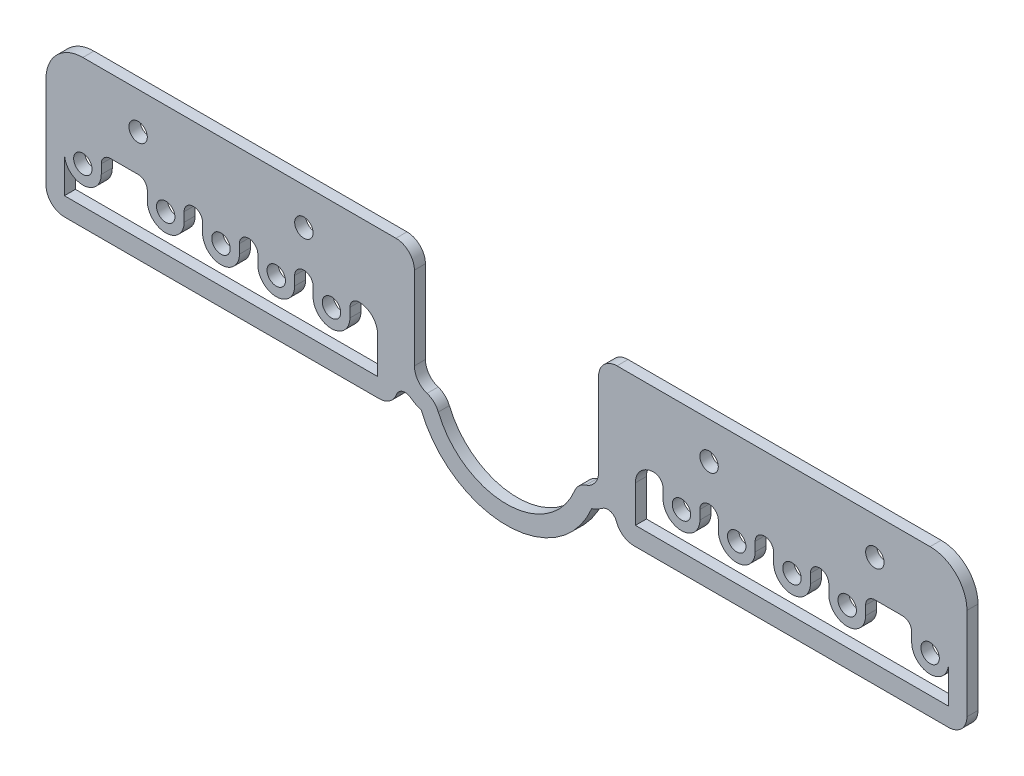
SolidWorks part; units mm, degrees
ref_plane "Front Plane" through (0, 0, 0) normal (0, 0, 1) x (1, 0, 0)
ref_plane "Top Plane" through (0, 0, 0) normal (0, 1, 0) x (1, 0, 0)
ref_plane "Right Plane" through (0, 0, 0) normal (1, 0, 0) x (0, 0, -1)
sketch "Sketch1" plane through (0, 0, 0) normal (0, 0, 1) x (1, 0, 0)
  line L0 (-40, 20) -> (-40, 55) construction
  line L4 (-250, -55) -> (-250, 3.1783)
  line L8 (-50, 75) -> (-230, 75) construction
  line L17 (0, -20) -> (0, -40)
  line L25 (0, -65) -> (0, -75)
  line L26 (0, 75) -> (0, -75) construction
  line L27 (-50, 95) -> (50, 95) construction
  line L34 (0, -75) -> (-230, -75)
  line L156 (-50, 75) -> (-230, 75) construction
  line L161 (0, -40) -> (0, -65)
  line L165 (-164.3309, 75) -> (-60, 75)
  line L167 (-230, 75) -> (-220, 75)
  line L171 (-250, 3.1783) -> (-250, 55)
  line L172 (-220, 75) -> (-164.3309, 75)
  line L173 (-50, 65) -> (-50, 20)
  arc A0 (-40, 20) -> (0, -20) centre (0, 20) ccw construction
  circle A1 centre (0, 20) radius 30 construction
  arc A4 (-230, -75) -> (-250, -55) centre (-230, -55) cw
  arc A5 (-250, 55) -> (-230, 75) centre (-230, 55) cw
  arc A124 (0, -20) -> (-37, 4.8013) centre (0, 20) cw
  arc A125 (-60, 75) -> (-50, 65) centre (-60, 65) cw
  arc A126 (-43.125, 10.5008) -> (-50, 20) centre (-40, 20) cw
  arc A127 (-37, 4.8013) -> (-43.125, 10.5008) centre (-46.25, 1.0016) ccw
  point P0 (0, 0)
  point P10 (-50, 10)
  point P11 (0, 50)
  point P30 (-40, 75)
  point P45 (0, -30)
  point P74 (0, 95)
  dimension "D3" = 80
  dimension "D4" = 60
  dimension "D6" = 55
  dimension "D7" = 75
  dimension "D10" = 10
  dimension "D11" = 20
  dimension "D8" = 10
  dimension "D5" = 10
  dimension "D9" = 20
  dimension "D13" = 210
  dimension "D16" = 100
  dimension "D17" = 20
  dimension "D26" = 250
extrude "Boss-Extrude1" add sketch "Sketch1" along normal blind 6
mirror "Mirror1" about plane through (0, -20, 6) normal (-1, 0, 0) of "Boss-Extrude1"
sketch "Sketch3" plane through (0, 0, 6) normal (0, 0, 1) x (1, 0, 0)
  line L3 (50, 20) -> (50, 65) construction
  line L4 (50, 20) -> (50, 65) construction
  line L7 (-60, 75) -> (-230, 75) construction
  line L8 (-250, 55) -> (-250, -55) construction
  line L9 (250, 55) -> (250, -55) construction
  circle A2 centre (110, 55) radius 5
  circle A3 centre (200, 55) radius 5
  circle A4 centre (-200, 55) radius 5
  circle A5 centre (-110, 55) radius 5
  dimension "D3" = 10
  dimension "D4" = 10
  dimension "D5" = 10
  dimension "D6" = 10
  dimension "D8" = 20
  dimension "D12" = 50
  dimension "D2" = 140
  dimension "D7" = 20
  dimension "D9" = 50
  dimension "D10" = 140
extrude "Cut-Extrude1" cut sketch "Sketch3" against normal through all contours A2 | A3 | A5 | A4 region at (110, 55, 6) region at (200, 55, 6) region at (-110, 55, 6)
sketch "Sketch4" plane through (0, 0, 6) normal (0, 0, 1) x (1, 0, 0)
  line L0 (-230, -75) -> (230, -75) construction
  line L1 (-70, 25) -> (-70, -55)
  line L2 (-50, 20) -> (-50, 65) construction
  line L3 (-60, 75) -> (-230, 75) construction
  line L7 (-240, -55) -> (-240, 25)
  line L8 (-250, 55) -> (-250, -55) construction
  line L9 (-210, -65) -> (-190, -65)
  line L10 (-115, 25) -> (-115, 30)
  line L11 (-110, 35) -> (-80, 35)
  line L12 (-220, 25) -> (-220, 30)
  line L13 (-215, 35) -> (-140, 35)
  line L14 (-135, 30) -> (-135, 25)
  line L15 (-230, -65) -> (-210, -65)
  line L16 (-110, -65) -> (-90, -65)
  line L17 (0, 0) -> (0, -75) construction
  line L18 (-190, -65) -> (-110, -65)
  line L19 (90, -65) -> (80, -65)
  line L20 (190, -65) -> (110, -65)
  line L21 (-90, -65) -> (-80, -65)
  line L22 (110, -65) -> (90, -65)
  line L23 (230, -65) -> (210, -65)
  line L24 (230, 25) -> (125, 25) construction
  line L30 (221.3397, 20) -> (133.6603, 20)
  line L32 (110, 35) -> (80, 35)
  line L33 (115, 25) -> (115, 30)
  line L35 (210, -65) -> (190, -65)
  line L36 (240, -55) -> (240, 25)
  line L37 (70, 25) -> (70, -55)
  line L38 (125, 35) -> (230, 35)
  line L39 (230, 20) -> (125, 20) construction
  circle A0 centre (-230, 25) radius 5
  circle A3 centre (-125, 25) radius 5
  arc A6 (-230, -65) -> (-240, -55) centre (-230, -55) cw
  arc A8 (-222.2775, 18.6468) -> (-231.6408, 15.1355) centre (-230, 25) ccw
  arc A9 (-127.2754, 15.2623) -> (-127.1893, 15.2426) centre (-125, 25) ccw
  arc A12 (-110, 35) -> (-115, 30) centre (-110, 30) ccw
  arc A13 (-140, 35) -> (-135, 30) centre (-140, 30) cw
  arc A14 (-215, 35) -> (-220, 30) centre (-215, 30) ccw
  arc A15 (-70, -55) -> (-80, -65) centre (-80, -55) cw
  arc A16 (-70, 25) -> (-80, 35) centre (-80, 25) ccw
  arc A17 (-117.6445, 18.2253) -> (-134.5708, 22.1017) centre (-125, 25) ccw
  arc A19 (-231.6408, 15.1355) -> (-222.2775, 18.6468) centre (-230, 25) ccw
  arc A20 (-134.5708, 22.1017) -> (-117.3815, 18.5225) centre (-125, 25) ccw
  arc A21 (133.6603, 20) -> (117.3815, 18.5225) centre (125, 25) cw
  arc A22 (231.6408, 15.1355) -> (222.2775, 18.6468) centre (230, 25) cw
  arc A23 (117.6445, 18.2253) -> (125, 35) centre (125, 25) cw
  arc A24 (70, 25) -> (80, 35) centre (80, 25) cw
  arc A25 (70, -55) -> (80, -65) centre (80, -55) ccw
  arc A26 (230, 35) -> (231.6408, 15.1355) centre (230, 25) cw
  arc A28 (110, 35) -> (115, 30) centre (110, 30) cw
  arc A29 (127.2754, 15.2623) -> (127.1893, 15.2426) centre (125, 25) cw
  arc A30 (222.2775, 18.6468) -> (221.3397, 20) centre (230, 25) cw
  arc A31 (230, -65) -> (240, -55) centre (230, -55) ccw
  circle A32 centre (125, 25) radius 5
  circle A33 centre (230, 25) radius 5
  point P0 (0, -75)
  dimension "D1" = 10
  dimension "D13" = 10
  dimension "D14" = 20
  dimension "D10" = 5
  dimension "D15" = 5
  dimension "D17" = 10
  dimension "D2" = 230
  dimension "D4" = 5
  dimension "D5" = 125
  dimension "D8" = 50
  dimension "D9" = 10
  dimension "D11" = 20
  dimension "D12" = 80
  dimension "D16" = 80
extrude "Cut-Extrude2" cut sketch "Sketch4" against normal through all contours A20 A17 L14 A13 L13 A14 L12 A8 A19 L7 A6 L15 L9 L18 L16 L21 A15 L1 A16 L11 A12 L10 A9 | A0 | A3 region at (-154.1168, -16.7892, 6) region at (-230, 25, 6) region at (-125, 25, 6)
sketch "Sketch8" plane through (0, 0, 6) normal (0, 0, 1) x (1, 0, 0)
  line L0 (-60, 0) -> (-60, -65)
  line L2 (-60, -65) -> (60, -65)
  line L3 (60, -65) -> (60, 0)
  line L4 (-230, -65) -> (-80, -65) construction
  arc A0 (43.125, 10.5008) -> (50, 20) centre (40, 20) ccw construction
  arc A1 (43.125, 10.5008) -> (37, 4.8013) centre (46.25, 1.0016) ccw construction
  arc A2 (-37, 4.8013) -> (-43.125, 10.5008) centre (-46.25, 1.0016) ccw construction
  arc A3 (-50, 20) -> (-43.125, 10.5008) centre (-40, 20) ccw construction
  arc A4 (-37, 4.8013) -> (37, 4.8013) centre (0, 20) ccw construction
  arc A5 (43.125, 10.5008) -> (50, 20) centre (40, 20) ccw construction
  arc A6 (43.125, 10.5008) -> (37, 4.8013) centre (46.25, 1.0016) ccw construction
  arc A7 (-37, 4.8013) -> (-43.125, 10.5008) centre (-46.25, 1.0016) ccw construction
  arc A8 (-50, 20) -> (-43.125, 10.5008) centre (-40, 20) ccw construction
  arc A9 (-37, 4.8013) -> (37, 4.8013) centre (0, 20) ccw construction
  arc A10 (-52, 4) -> (-46.25, 1.0016) centre (-40, 20) ccw
  arc A11 (-46.25, 1.0016) -> (-46.25, 1.0016) centre (-46.25, 1.0016) ccw
  arc A12 (-46.25, 1.0016) -> (46.25, 1.0016) centre (0, 20) ccw
  arc A13 (46.25, 1.0016) -> (46.25, 1.0016) centre (46.25, 1.0016) ccw
  arc A14 (46.25, 1.0016) -> (52, 4) centre (40, 20) ccw
  arc A15 (46.25, 1.0016) -> (60, 20) centre (40, 20) ccw construction
  arc A16 (60, 0) -> (52, 4) centre (55, 0) ccw
  arc A17 (-60, 20) -> (-46.25, 1.0016) centre (-40, 20) ccw construction
  arc A18 (-60, 0) -> (-52, 4) centre (-55, 0) cw
  dimension "D2" = 5
  dimension "D1" = 10
extrude "Cut-Extrude5" cut sketch "Sketch8" against normal through all
fillet "Fillet5" radius 5 1 edges at (-60, -65, 3)
fillet "Fillet6" radius 5 1 edges at (60, -65, 3)
mirror "Mirror2" about plane through (0, 0, 0) normal (1, 0, 0) of "Cut-Extrude2"
sketch "Sketch9" plane through (0, 0, 6) normal (0, 0, 1) x (1, 0, 0)
  line L0 (-250, 5) -> (-70, 5)
  line L1 (-250, 55) -> (-250, -55) construction
  line L2 (250, 55) -> (250, -55) construction
  line L3 (250, 5) -> (250, -5)
  line L4 (250, -5) -> (70, -5)
  line L5 (-250, -5) -> (-250, 5)
  line L6 (-215, 35) -> (-140, 35) construction
  line L7 (-70, 5) -> (-70, -5)
  line L8 (-70, 25) -> (-70, -55) construction
  line L9 (70, 5) -> (70, -5)
  line L10 (70, 25) -> (70, -55) construction
  line L11 (70, 5) -> (250, 5)
  line L12 (-70, -5) -> (-250, -5)
  dimension "D1" = 10
  dimension "D2" = 30
extrude "Boss-Extrude2" add sketch "Sketch9" against normal up to surface (6 mm away) up to face at (225, 25, 0)
sketch "Sketch10" plane through (0, 0, 6) normal (0, 0, 1) x (1, 0, 0)
  line L0 (-240, -5) -> (-250, -5)
  line L1 (-250, 55) -> (-250, -55) construction
  line L2 (-250, -5) -> (-250, -78.6459)
  line L3 (-250, -78.6459) -> (262.9132, -78.6459)
  line L4 (262.9132, -78.6459) -> (262.9132, -5)
  line L5 (262.9132, -5) -> (43.3013, -5)
  line L7 (-43.3013, -5) -> (-240, -5)
  arc A0 (-46.25, 1.0016) -> (46.25, 1.0016) centre (0, 20) ccw construction
  arc A1 (-43.3013, -5) -> (43.3013, -5) centre (0, 20) ccw
  point P14 (0, 0)
extrude "Cut-Extrude6" cut sketch "Sketch10" against normal through all
fillet "Fillet7" radius 10 4 edges at (60, -5, 3) (250, -5, 3) (-60, -5, 3) (-250, -5, 3)
sketch "Sketch11" plane through (0, 0, 6) normal (0, 0, 1) x (1, 0, 0)
  line L0 (-115, 25) -> (-115, 30) construction
  line L1 (-135, 30) -> (-135, 25) construction
  line L2 (-115, 25) -> (-115, 30)
  line L3 (-135, 30) -> (-135, 25)
  line L4 (-145, 25) -> (-145, 30)
  line L5 (-165, 30) -> (-165, 25)
  line L6 (-175, 25) -> (-175, 30)
  line L7 (-195, 30) -> (-195, 25)
  line L8 (-85, 25) -> (-85, 30)
  line L9 (-105, 30) -> (-105, 25)
  line L10 (-200, 35) -> (-200, 37.5031)
  line L11 (-200, 37.5031) -> (-80, 37.5031)
  line L12 (-80, 37.5031) -> (-80, 35)
  arc A0 (-110, 35) -> (-115, 30) centre (-110, 30) ccw construction
  circle A1 centre (-125, 25) radius 5 construction
  arc A2 (-135, 25) -> (-115, 25) centre (-125, 25) ccw construction
  arc A3 (-135, 30) -> (-140, 35) centre (-140, 30) ccw construction
  arc A4 (-110, 35) -> (-115, 30) centre (-110, 30) ccw
  circle A5 centre (-125, 25) radius 5
  arc A6 (-135, 25) -> (-115, 25) centre (-125, 25) ccw
  arc A7 (-135, 30) -> (-140, 35) centre (-140, 30) ccw
  arc A8 (-140, 35) -> (-145, 30) centre (-140, 30) ccw
  circle A9 centre (-155, 25) radius 5
  arc A10 (-165, 25) -> (-145, 25) centre (-155, 25) ccw
  arc A11 (-165, 30) -> (-170, 35) centre (-170, 30) ccw
  arc A12 (-170, 35) -> (-175, 30) centre (-170, 30) ccw
  circle A13 centre (-185, 25) radius 5
  arc A14 (-195, 25) -> (-175, 25) centre (-185, 25) ccw
  arc A15 (-195, 30) -> (-200, 35) centre (-200, 30) ccw
  arc A16 (-80, 35) -> (-85, 30) centre (-80, 30) ccw
  circle A17 centre (-95, 25) radius 5
  arc A18 (-105, 25) -> (-85, 25) centre (-95, 25) ccw
  arc A19 (-105, 30) -> (-110, 35) centre (-110, 30) ccw
  dimension "D1" = 3
  dimension "D2" = 2
extrude "Boss-Extrude3" add sketch "Sketch11" against normal up to surface (6 mm away) contours A19 L9 A18 L8 A16 L12 L11 L10 A15 L7 A14 L6 A12 A11 L5 A10 L4 A8 A7 L3 A6 L2 A4 A17 A13 A9 A5 region at (-125, 16.2209, 6) up to face at (0, 21.7684, 0)
mirror "Mirror3" about plane through (0, 0, 0) normal (1, 0, 0) of "Boss-Extrude3"
